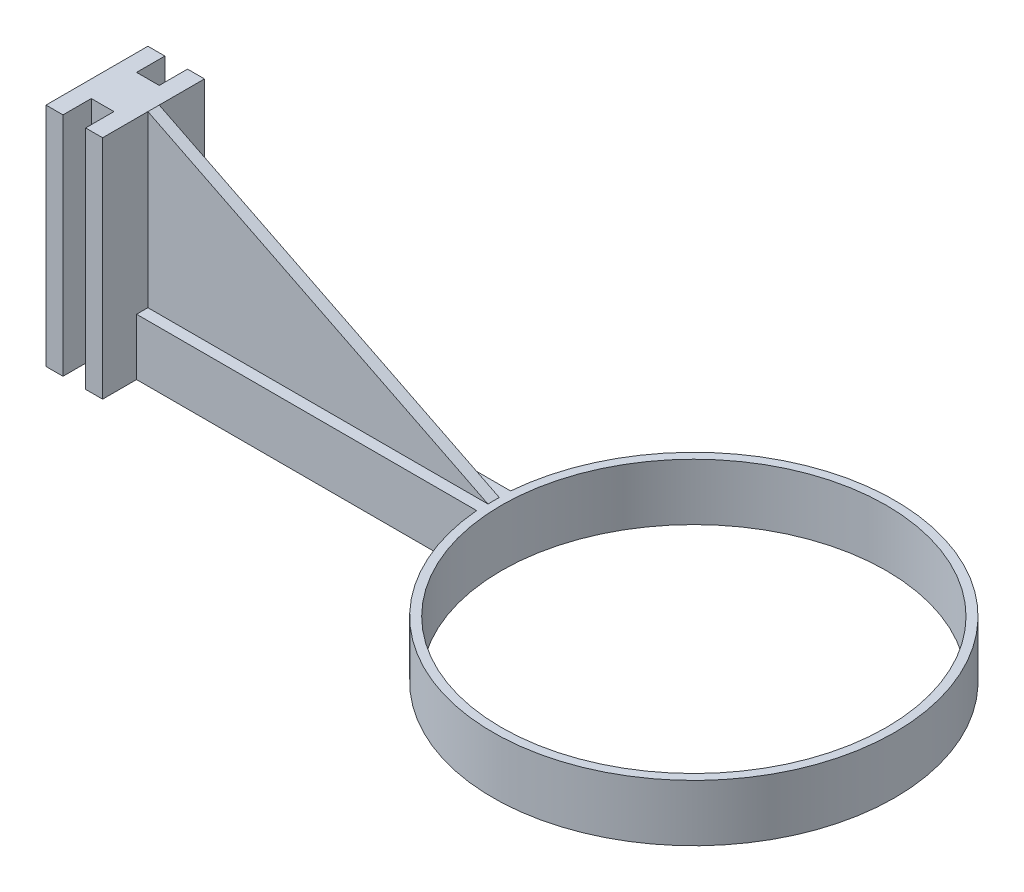
SolidWorks part; units mm, degrees
ref_plane "Front Plane" through (0, 0, 0) normal (0, 0, 1) x (1, 0, 0)
ref_plane "Top Plane" through (0, 0, 0) normal (0, 1, 0) x (1, 0, 0)
ref_plane "Right Plane" through (0, 0, 0) normal (1, 0, 0) x (0, 0, -1)
sketch "Sketch1" plane through (0, 0, 0) normal (0, 1, 0) x (1, 0, 0)
  line L0 (0, 17.25) -> (44, 17.25) construction
  line L1 (1, 0) -> (43, 0)
  line L2 (0, 12) -> (0, 22.5)
  line L3 (1, 34.5) -> (43, 34.5)
  line L4 (44, 1) -> (44, 33.5)
  line L5 (0.5, -1) -> (43.5, -1)
  line L6 (-1, 0.5) -> (-1, 34)
  line L7 (0.5, 35.5) -> (43.5, 35.5)
  line L8 (45, 0.5) -> (45, 34)
  line L9 (0.75, 24) -> (8.25, 24)
  line L10 (8, 23.25) -> (0.75, 23.25)
  line L11 (8.75, 22.5) -> (8.75, 12)
  line L12 (8, 11.25) -> (0.75, 11.25)
  line L13 (0, 1) -> (0, 9.75)
  line L14 (0, 24.75) -> (0, 33.5)
  line L15 (0, 24.75) -> (0, 22.5)
  line L16 (9.5, 22.75) -> (9.5, 11.75)
  line L17 (8.25, 10.5) -> (0.75, 10.5)
  line L18 (0, 12) -> (0, 9.75)
  line L19 (3, 35.5) -> (3, 34.5)
  line L20 (-1, 31.5) -> (0, 31.5)
  line L21 (44, 31.5) -> (45, 31.5)
  line L22 (41, 34.5) -> (41, 35.5)
  line L23 (41, 0) -> (41, -1)
  line L24 (3, 0) -> (3, -1)
  line L25 (0, 3) -> (-1, 3)
  line L26 (28.2, 28.7) -> (38.2, 28.7)
  line L27 (28.2, 28.7) -> (28.2, 24.7)
  line L28 (28.2, 24.7) -> (38.2, 24.7)
  line L29 (38.2, 28.7) -> (38.2, 24.7)
  line L30 (44, 3) -> (45, 3)
  arc A0 (0, 1) -> (1, 0) centre (1, 1) ccw
  arc A1 (43, 0) -> (44, 1) centre (43, 1) ccw
  arc A2 (44, 33.5) -> (43, 34.5) centre (43, 33.5) ccw
  arc A3 (1, 34.5) -> (0, 33.5) centre (1, 33.5) ccw
  arc A4 (0.5, -1) -> (-1, 0.5) centre (0.5, 0.5) cw
  arc A5 (-1, 34) -> (0.5, 35.5) centre (0.5, 34) cw
  arc A6 (43.5, -1) -> (45, 0.5) centre (43.5, 0.5) ccw
  arc A7 (43.5, 35.5) -> (45, 34) centre (43.5, 34) cw
  arc A8 (9.5, 11.75) -> (8.25, 10.5) centre (8.25, 11.75) cw
  arc A9 (9.5, 22.75) -> (8.25, 24) centre (8.25, 22.75) ccw
  arc A10 (0.75, 23.25) -> (0, 22.5) centre (0.75, 22.5) ccw
  arc A11 (0, 12) -> (0.75, 11.25) centre (0.75, 12) ccw
  arc A12 (8.75, 12) -> (8, 11.25) centre (8, 12) cw
  arc A13 (8, 23.25) -> (8.75, 22.5) centre (8, 22.5) cw
  arc A14 (0.75, 24) -> (0, 24.75) centre (0.75, 24.75) cw
  arc A15 (0.75, 10.5) -> (0, 9.75) centre (0.75, 9.75) ccw
  arc A16 (44, 19.75) -> (44, 14.75) centre (44, 17.25) cw
  arc A17 (0, 19.75) -> (0, 14.75) centre (0, 17.25) ccw
  point P7 (0, 0)
  point P10 (44, 0)
  point P13 (44, 34.5)
  point P22 (-1, -1)
  point P27 (45, -1)
  point P30 (45, 35.5)
  point P33 (4, 17.25)
  point P36 (0, 24)
  point P44 (9.5, 10.5)
  point P47 (9.5, 24)
  point P61 (0, 10.5)
  dimension "D3" = 0.75
  dimension "D6" = 10
  dimension "D5" = 5.8
  dimension "D2" = 0.75
  dimension "D1" = 7.25
  dimension "D9" = 3
  dimension "D4" = 0.75
  dimension "D7" = 4
  dimension "D8" = 5.8
  dimension "D10" = 3
  dimension "D11" = 3
  dimension "D12" = 3
sketch "Sketch8" plane through (0, 0, 0) normal (0, 1, 0) x (1, 0, 0)
  line L0 (0, 0) -> (-38.2686, 0) construction
  line L1 (-51.2202, 2) -> (-51.2202, 4.5)
  line L2 (-51.2202, 4.5) -> (-52.7202, 4.5)
  line L3 (-52.7202, 4.5) -> (-52.7202, -4.5)
  line L4 (-52.7202, -4.5) -> (-51.2202, -4.5)
  line L5 (-51.2202, -4.5) -> (-51.2202, -2)
  line L6 (-51.2202, 2) -> (-49.2202, 2)
  line L7 (-51.2202, -2) -> (-49.2202, -2)
  line L8 (-49.2202, -2) -> (-49.2202, -4.5)
  line L9 (-49.2202, -4.5) -> (-47.7202, -4.5)
  line L10 (-47.7202, -4.5) -> (-47.7202, 4.5)
  line L11 (-47.7202, 4.5) -> (-49.2202, 4.5)
  line L12 (-49.2202, 4.5) -> (-49.2202, 2)
  line L13 (-47.7202, 1.5) -> (-17.6865, 1.5)
  line L14 (-47.7202, -1.5) -> (-17.6865, -1.5)
  circle A0 centre (0, 0) radius 17
  circle A1 centre (0, 0) radius 17.75
  dimension "D1" = 0.75
  dimension "D2" = 1.5
  dimension "D3" = 2.5
  dimension "D4" = 2
  dimension "D5" = 2
  dimension "D6" = 1.5
  dimension "D7" = 1.5
extrude "Boss-Extrude10" add sketch "Sketch8" along normal blind 5 contours A1 L0 A0 | L0 A1 A0 | L0 A1 L13 L10 | A1 L0 L10 L14 region at (-17.2325, 0, -0.7294) region at (-18.0357, 0, 0.7634)
extrude "Boss-Extrude11" add sketch "Sketch8<3>" along normal blind 20 contours L10 L0 L3 L4 L5 L7 L8 L9 | L0 L10 L11 L12 L6 L1 L2 L3 region at (-50.2202, 0, 0)
sketch "Sketch8<3>" plane through (0, 0, 0) normal (0, 1, 0) x (1, 0, 0) same geometry as "Sketch8"
sketch "Sketch9" plane through (0, 0, 1.5) normal (0, 0, 1) x (1, 0, 0)
  line L0 (-17.6865, 5) -> (-47.7202, 5)
  line L1 (-47.7202, 5) -> (-47.7202, 20)
  line L2 (-47.7202, 20) -> (-17.6865, 5)
extrude "Boss-Extrude13" add sketch "Sketch9" against normal blind 1 from offset 1 offset against normal yes
